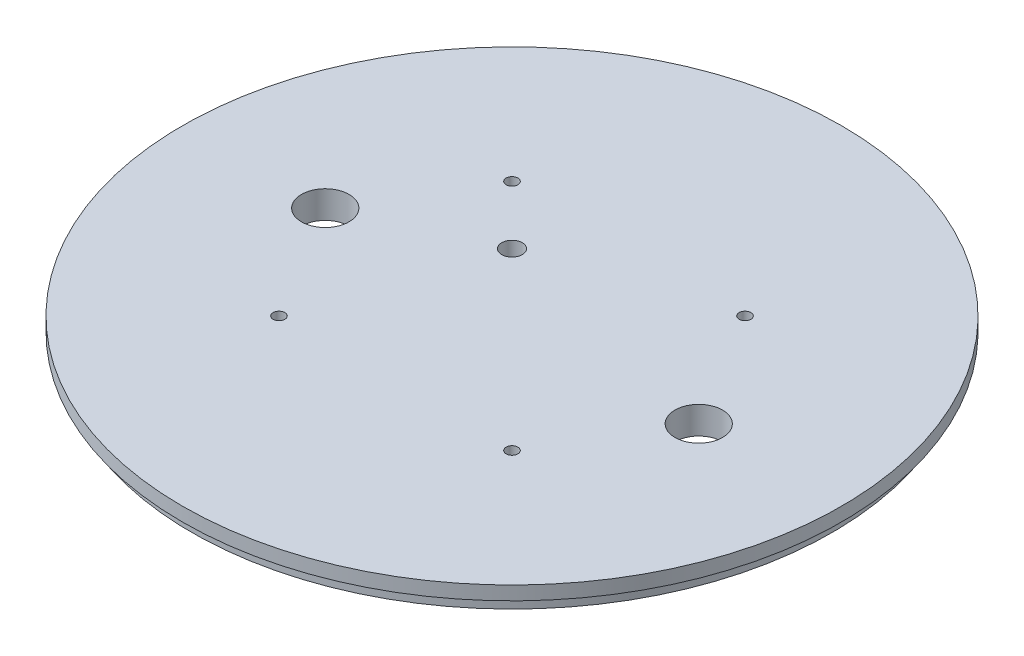
SolidWorks part; units mm, degrees
material "6061-T6 (SS)"
ref_plane "Front Plane" through (0, 0, 0) normal (0, 0, 1) x (1, 0, 0)
ref_plane "Top Plane" through (0, 0, 0) normal (0, 1, 0) x (1, 0, 0)
ref_plane "Right Plane" through (0, 0, 0) normal (1, 0, 0) x (0, 0, -1)
sketch "Sketch1" plane through (0, 0, 0) normal (0, 1, 0) x (1, 0, 0)
  line L0 (0, -76.2) -> (0, 76.2) construction
  line L1 (-76.2, 0) -> (76.2, 0) construction
  line L2 (-26.9408, 26.9408) -> (0, 0) construction
  line L3 (0, 56.7387) -> (0, 29.6936) construction
  line L4 (3.6407, 56.7387) -> (3.6407, 29.6936) construction
  line L5 (-3.6407, 56.7387) -> (-3.6407, 29.6936) construction
  line L6 (0, -56.7387) -> (0, -29.6936) construction
  line L7 (3.6407, -56.7387) -> (3.6407, -29.6936) construction
  line L8 (-3.6407, -56.7387) -> (-3.6407, -29.6936) construction
  line L9 (-53.8815, -53.8815) -> (54.3236, 54.3236) construction
  circle A0 centre (0, 0) radius 76.2
  circle A1 centre (0, 0) radius 3.175 construction
  circle A2 centre (43.18, 0) radius 5.5
  circle A3 centre (-43.18, 0) radius 5.5
  circle A4 centre (-26.9408, 26.9408) radius 1.3589
  arc A6 (3.6407, 56.7387) -> (-3.6407, 56.7387) centre (0, 56.7387) ccw construction
  arc A7 (-3.6407, 29.6936) -> (3.6407, 29.6936) centre (0, 29.6936) ccw construction
  arc A8 (3.6407, -56.7387) -> (-3.6407, -56.7387) centre (0, -56.7387) cw construction
  arc A9 (-3.6407, -29.6936) -> (3.6407, -29.6936) centre (0, -29.6936) cw construction
  circle A10 centre (26.9408, -26.9408) radius 1.3589
  circle A11 centre (-13.4704, 13.4704) radius 2.3813
  circle A12 centre (-26.9408, -26.9408) radius 1.3589
  circle A13 centre (26.9408, 26.9408) radius 1.3589
  circle A14 centre (-26.9408, 26.9408) radius 1.3589
  circle A15 centre (26.9408, -26.9408) radius 1.3589
  circle A16 centre (26.9408, 26.9408) radius 1.3589
  circle A17 centre (-26.9408, -26.9408) radius 1.3589
  point P16 (0, 43.2162)
  point P19 (0, 0)
  point P26 (0, -43.2162)
  point P50 (0, 0)
  dimension "D1" = 152.4
  dimension "D2" = 6.35
  dimension "D3" = 11
  dimension "D5" = 2.7178
  dimension "D8" = 4.7625
  dimension "D6" = 38.1
  dimension "D7" = 45
  dimension "D4" = 45
  dimension "D9" = 43.18
  dimension "D10" = 4
extrude "Boss-Extrude1" add sketch "Sketch1" along normal blind 6.35 contours A0 A13 A10 A4 A2 A3 A11 A12 region at (0.0133, 0, 0.0133)
sketch "Sketch2" plane through (0, 0, 0) normal (0, -1, 0) x (1, 0, 0)
  circle A0 centre (0, 0) radius 76.2
  circle A1 centre (0, 0) radius 74.041
  dimension "D1" = 152.4
  dimension "D2" = 148.082
extrude "Cut-Extrude1" cut sketch "Sketch2" against normal blind 3.175
sketch "Sketch3" plane through (0, 6.35, 0) normal (0, 1, 0) x (1, 0, 0)
  line L0 (0, 76.2) -> (0, -76.2) construction
  line L1 (-76.2, 0) -> (76.2, 0) construction
  line L2 (0, 34.798) -> (0, 13.97) construction
  line L3 (3.2385, 34.798) -> (3.2385, 13.97)
  line L4 (-3.2385, 34.798) -> (-3.2385, 13.97)
  line L5 (0, -34.798) -> (0, -13.97) construction
  line L6 (3.2385, -34.798) -> (3.2385, -13.97)
  line L7 (-3.2385, -34.798) -> (-3.2385, -13.97)
  circle A0 centre (0, 0) radius 76.2 construction
  arc A1 (3.2385, 34.798) -> (-3.2385, 34.798) centre (0, 34.798) ccw
  arc A2 (-3.2385, 13.97) -> (3.2385, 13.97) centre (0, 13.97) ccw
  arc A3 (3.2385, -34.798) -> (-3.2385, -34.798) centre (0, -34.798) cw
  arc A4 (-3.2385, -13.97) -> (3.2385, -13.97) centre (0, -13.97) cw
  point P7 (0, 13.97)
  point P8 (0, 34.798)
  point P12 (0, 24.384)
  point P17 (0, 0)
  point P20 (0, -24.384)
  point P25 (0, -34.798)
  point P26 (0, -13.97)
  point P27 (0, 0)
  point P28 (0, 0)
  point P29 (0, 0)
  point P30 (0, 0)
  point P31 (0, 0)
  point P32 (0, 0)
  dimension "D1" = 13.97
  dimension "D2" = 20.828
  dimension "D3" = 6.477
extrude "Cut-Extrude2" cut sketch "Sketch3" against normal blind 3.556 from offset 3.175 offset against normal yes
equation "\"leadDist\"=1.5"
equation "\"Lead_Screw_Dist\" = 3.4in"
equation "\"Lead_Screw_Diam\" = 11mm"
equation "\"D3@Sketch1\"=\"Lead_Screw_Diam\""
equation "\"D9@Sketch1\"=\"Lead_Screw_Dist\"/2"
